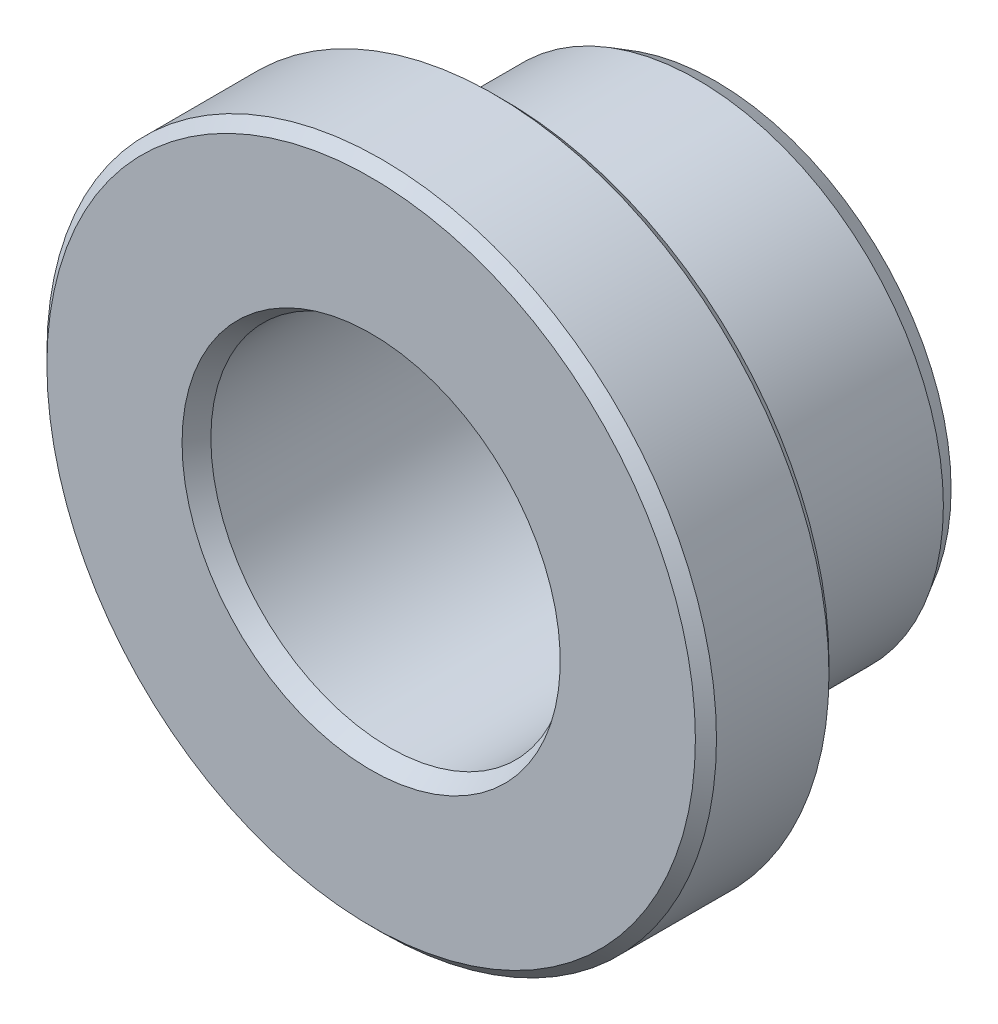
SolidWorks part; units mm, degrees
material "Delrin 150"
ref_plane "Front Plane" through (0, 0, 0) normal (0, 0, 1) x (1, 0, 0)
ref_plane "Top Plane" through (0, 0, 0) normal (0, 1, 0) x (1, 0, 0)
ref_plane "Right Plane" through (0, 0, 0) normal (1, 0, 0) x (0, 0, -1)
ref_axis "Axis1" through (0, 0, -88.99) along (0, 0, 1)
ref_axis "Axis2" through (0, -55, 0) along (0, 1, 0)
ref_axis "Axis3" through (-88.99, 0, 0) along (1, 0, 0)
sketch "Sketch1" plane through (0, 0, 0) normal (1, 0, 0) x (0, 0, -1)
  line L0 (0, 23.8125) -> (9.5, 23.8125)
  line L1 (9.5, 23.8125) -> (9.5, 17.5)
  line L2 (9.5, 17.5) -> (24.5, 17.5)
  line L3 (24.5, 17.5) -> (24.5, 12.7)
  line L4 (24.5, 12.7) -> (0, 12.7)
  line L5 (0, 12.7) -> (0, 23.8125)
  line L6 (0, 0) -> (40.3343, 0) construction
  dimension "D1" = 25.4
  dimension "D2" = 47.625
  dimension "D3" = 35
  dimension "D4" = 9.5
  dimension "D5" = 15
revolve "Revolve1" add sketch "Sketch1" angle 360 about L6
chamfer "Chamfer1" distance 0.75 angle 60 3 edges at (17.5, 0, -24.5) (12.7, 0, 0) (12.7, 0, -24.5) first distance on face at (17.5, 0, -24.5) first distance on face at (12.7, 0, 0)
chamfer "Chamfer2" distance 0.75 angle 45 2 edges at (23.8125, 0, -9.5) (23.8125, 0, 0)
